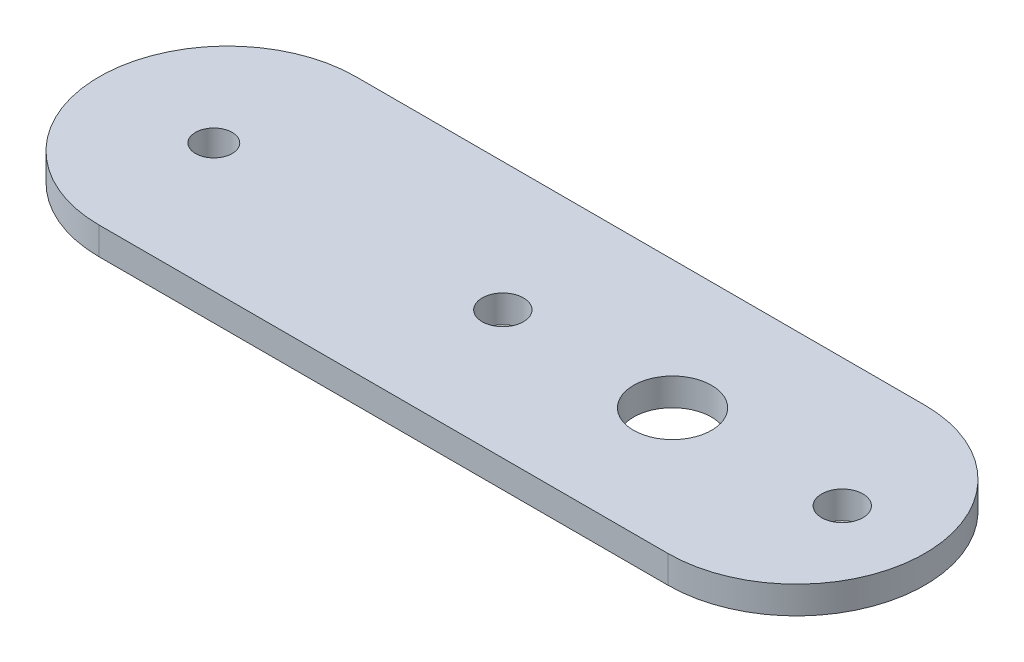
SolidWorks part; units mm, degrees
ref_plane "前视" through (0, 0, 0) normal (0, 0, 1) x (1, 0, 0)
ref_plane "上视" through (0, 0, 0) normal (0, 1, 0) x (1, 0, 0)
ref_plane "右视" through (0, 0, 0) normal (1, 0, 0) x (0, 0, -1)
sketch "草图1" plane through (0, 0, 0) normal (0, 1, 0) x (1, 0, 0)
  line L1 (-45, 14) -> (45, 14)
  line L2 (-45, 14) -> (-45, -14)
  line L3 (-45, -14) -> (45, -14)
  line L4 (45, 14) -> (45, -14)
  line L5 (-45, 14) -> (45, -14) construction
  line L6 (-45, -14) -> (45, 14) construction
  circle A0 centre (17.5, 0) radius 4.25
  circle A1 centre (-32.5, 0) radius 2
  point P0 (0, 0)
  dimension "D3" = 4
  dimension "D4" = 8.5
  dimension "D1" = 90
  dimension "D2" = 77.5
  dimension "28" = 28
  dimension "D5" = 50
extrude "凸台-拉伸1" add sketch "草图1" along normal blind 3
sketch "草图2" plane through (0, 3, 0) normal (0, 1, 0) x (1, 0, 0)
  text T0 "             <b>2</b>"
extrude "凸台-拉伸2" [suppressed] add sketch "草图2" along normal blind 0.5
sketch "草图3" plane through (0, 3, 0) normal (0, 1, 0) x (1, 0, 0)
  circle A0 centre (36, 0) radius 2.25
  circle A1 centre (-1, 0) radius 2.25
  point P4 (17.5, 0)
  dimension "D3" = 4.5
  dimension "D4" = 4.5
  dimension "D1" = 37
  dimension "D2" = 18.5
extrude "切除-拉伸1" cut sketch "草图3" against normal up to next
fillet "圆角1" 2 edges at (45, 1.5, -14) (45, 1.5, 14) type full round first side face at (0, 1.5, -14) second side face at (0, 1.5, 14) middle face at (45, 1.5, 0)
fillet "圆角2" 2 edges at (-45, 1.5, -14) (-45, 1.5, 14) type full round first side face at (-7, 1.5, -14) second side face at (-7, 1.5, 14) middle face at (-45, 1.5, 0)
